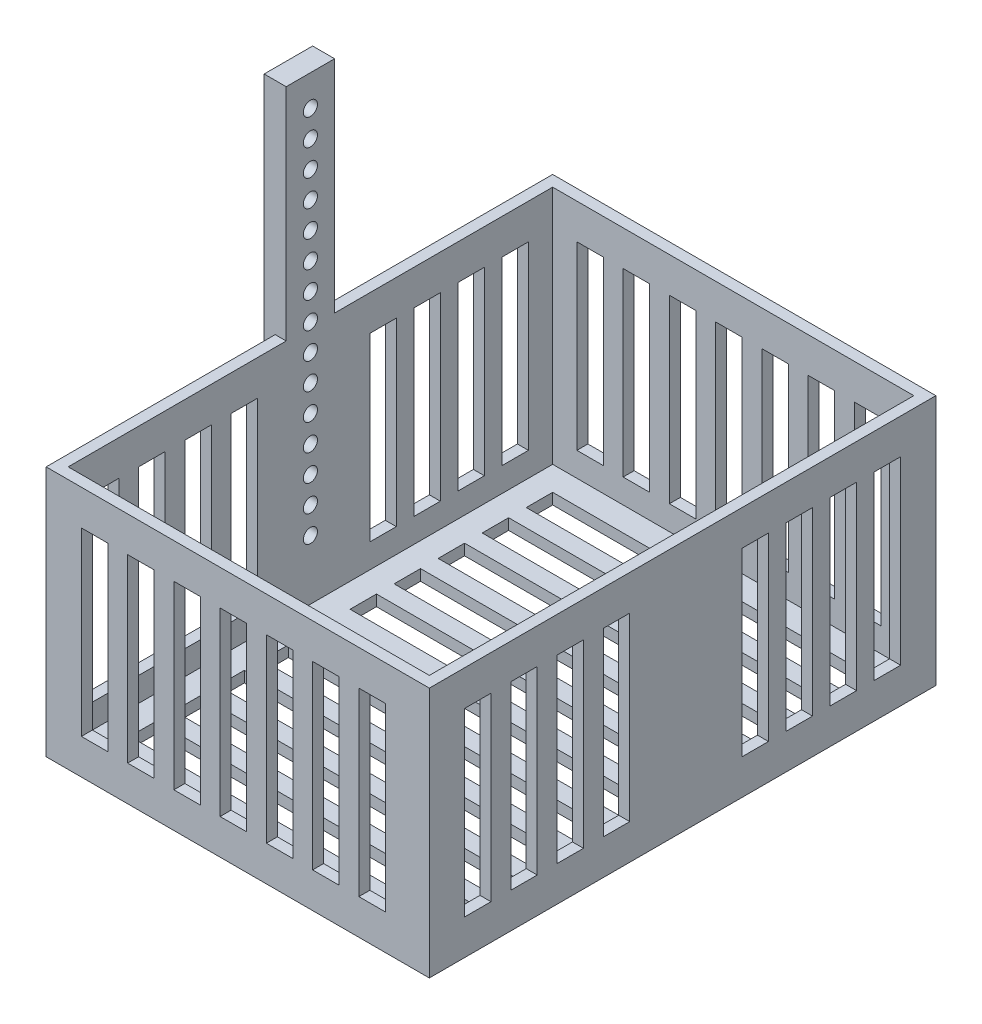
SolidWorks part; units mm, degrees
ref_plane "Front Plane" through (0, 0, 0) normal (0, 0, 1) x (1, 0, 0)
ref_plane "Top Plane" through (0, 0, 0) normal (0, 1, 0) x (1, 0, 0)
ref_plane "Right Plane" through (0, 0, 0) normal (1, 0, 0) x (0, 0, -1)
sketch "Sketch1" plane through (0, 0, 0) normal (0, 1, 0) x (1, 0, 0)
  line L1 (-43.5, 57.5) -> (43.5, 57.5)
  line L2 (-43.5, 57.5) -> (-43.5, -57.5)
  line L3 (-43.5, -57.5) -> (43.5, -57.5)
  line L4 (43.5, 57.5) -> (43.5, -57.5)
  point P4 (0, 57.5)
  point P6 (-43.5, 0)
  dimension "D1" = 87
  dimension "D2" = 115
extrude "Boss-Extrude1" add sketch "Sketch1" against normal blind 2.5
sketch "Sketch2" plane through (0, 0, 0) normal (0, 1, 0) x (1, 0, 0)
  line L1 (-43.5, 57.5) -> (43.5, 57.5)
  line L2 (-43.5, 57.5) -> (-43.5, -57.5)
  line L3 (-43.5, -57.5) -> (43.5, -57.5)
  line L4 (43.5, 57.5) -> (43.5, -57.5)
  line L5 (41, -55) -> (-41, -55)
  line L6 (41, -55) -> (41, 55)
  line L7 (41, 55) -> (-41, 55)
  line L8 (-41, -55) -> (-41, 55)
  dimension "D1" = 2.5
  dimension "D2" = 2.5
  dimension "D3" = 2.5
  dimension "D4" = 2.5
extrude "Boss-Extrude2" add sketch "Sketch2" along normal blind 54.5
sketch "Sketch3" plane through (0, -2.5, 0) normal (0, -1, 0) x (1, 0, 0)
  line L0 (-41, -55) -> (-41, 55) construction
  line L1 (-41, -5.5) -> (-46, -5.5)
  line L2 (-41, -5.5) -> (-41, 5.5)
  line L3 (-41, 5.5) -> (-46, 5.5)
  line L4 (-46, -5.5) -> (-46, 5.5)
  point P6 (-41, 0)
  dimension "D1" = 11
  dimension "D2" = 5
extrude "Boss-Extrude3" add sketch "Sketch3" against normal through all
sketch "Sketch4" plane through (0, 54.5, 0) normal (0, 1, 0) x (1, 0, 0)
  line L0 (-41, 55) -> (-41, -55) construction
  line L1 (-46, 5.5) -> (-41, 5.5)
  line L2 (-46, 5.5) -> (-46, -5.5)
  line L3 (-46, -5.5) -> (-41, -5.5)
  line L4 (-41, 5.5) -> (-41, -5.5)
  line L5 (-43.5, -5.5) -> (-46, -5.5) construction
extrude "Boss-Extrude4" add sketch "Sketch4" along normal blind 50
sketch "Sketch5" plane through (-46, 0, 0) normal (-1, 0, 0) x (0, 0, 1)
  line L1 (5.5, -2.5) -> (-5.5, -2.5) construction
  circle A0 centre (0, 97.5) radius 1.6
  dimension "D1" = 3.2
  dimension "D2" = 100
extrude "Cut-Extrude1" cut sketch "Sketch5" against normal up to next
pattern_linear "LPattern1" count 15 spacing 6 along (0, -1, 0) of "Cut-Extrude1"
sketch "Sketch6" plane through (0, 0, 0) normal (0, 0, 1) x (1, 0, 0)
  line L0 (-43.5, -2.5) -> (-43.5, 54.5) construction
  line L1 (-35.5, 46.5) -> (-29.5, 46.5)
  line L2 (-35.5, 46.5) -> (-35.5, 5.5)
  line L3 (-35.5, 5.5) -> (-29.5, 5.5)
  line L4 (-29.5, 46.5) -> (-29.5, 5.5)
  line L5 (-43.5, 54.5) -> (43.5, 54.5) construction
  line L6 (-43.5, -2.5) -> (43.5, -2.5) construction
  dimension "D1" = 8
  dimension "D2" = 8
  dimension "D3" = 8
  dimension "D4" = 6
extrude "Cut-Extrude2" cut sketch "Sketch6" against normal through all both and the other way through all
pattern_linear "LPattern2" count 7 spacing 10.5 along (1, 0, 0) of "Cut-Extrude2"
sketch "Sketch7" plane through (0, 0, 0) normal (1, 0, 0) x (0, 0, -1)
  line L0 (-57.5, -2.5) -> (-57.5, 54.5) construction
  line L1 (-43.5, 46.5) -> (-49.5, 46.5)
  line L2 (-43.5, 46.5) -> (-43.5, 5.5)
  line L3 (-43.5, 5.5) -> (-49.5, 5.5)
  line L4 (-49.5, 46.5) -> (-49.5, 5.5)
  line L5 (-5.5, 54.5) -> (-57.5, 54.5) construction
  line L6 (-5.5, -2.5) -> (-57.5, -2.5) construction
  dimension "D1" = 8
  dimension "D2" = 8
  dimension "D3" = 6
  dimension "D4" = 8
extrude "Cut-Extrude3" cut sketch "Sketch7" along normal through all both and the other way through all
pattern_linear "LPattern3" count 4 spacing 10.5 along (0, 0, -1) of "Cut-Extrude3"
sketch "Sketch8" plane through (0, 0, 0) normal (1, 0, 0) x (0, 0, -1)
  line L0 (57.5, 54.5) -> (5.5, 54.5) construction
  line L1 (49.5, 46.5) -> (43.5, 46.5)
  line L2 (49.5, 46.5) -> (49.5, 5.5)
  line L3 (49.5, 5.5) -> (43.5, 5.5)
  line L4 (43.5, 46.5) -> (43.5, 5.5)
  line L5 (57.5, -2.5) -> (57.5, 54.5) construction
  line L6 (57.5, -2.5) -> (5.5, -2.5) construction
  dimension "D1" = 8
  dimension "D2" = 8
  dimension "D3" = 8
  dimension "D4" = 6
sketch "Sketch9" plane through (0, 0, 0) normal (0, 1, 0) x (1, 0, 0)
  line L0 (43.5, 57.5) -> (-43.5, 57.5) construction
  line L1 (-35.5, 49.5) -> (35.5, 49.5)
  line L2 (-35.5, 49.5) -> (-35.5, 43.5)
  line L3 (-35.5, 43.5) -> (35.5, 43.5)
  line L4 (35.5, 49.5) -> (35.5, 43.5)
  line L5 (-43.5, 57.5) -> (-43.5, 5.5) construction
  line L6 (43.5, -57.5) -> (43.5, 57.5) construction
  dimension "D1" = 8
  dimension "D2" = 8
  dimension "D3" = 8
  dimension "D4" = 6
extrude "Cut-Extrude4" cut sketch "Sketch8" against normal through all both and the other way through all
pattern_linear "LPattern4" count 4 spacing 10 along (0, 0, 1) of "Cut-Extrude4"
extrude "Cut-Extrude5" cut sketch "Sketch9" against normal through all both
pattern_linear "LPattern5" count 10 spacing 10 along (0, 0, 1) of "Cut-Extrude5"
equation "\"wall\"=2.5"
equation "\"D1@Sketch2\"=\"wall\""
equation "\"D2@Sketch2\"=\"wall\""
equation "\"D3@Sketch2\"=\"wall\""
equation "\"D4@Sketch2\"=\"wall\""
equation "\"D1@Boss-Extrude2\"=57-\"wall\""
